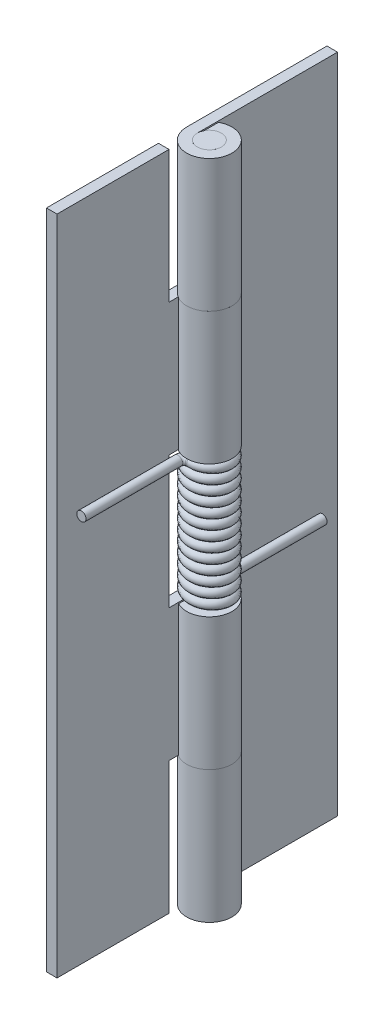
SolidWorks part; units mm, degrees
note: The reader was unsure of these and kept them because the rebuilt part matched: shared geometry of "Sketch12<2>", "Sketch13<2>".
ref_plane "Front Plane" through (0, 0, 0) normal (0, 0, 1) x (1, 0, 0)
ref_plane "Top Plane" through (0, 0, 0) normal (0, 1, 0) x (1, 0, 0)
ref_plane "Right Plane" through (0, 0, 0) normal (1, 0, 0) x (0, 0, -1)
sketch "Sketch1" plane through (0, 0, 0) normal (1, 0, 0) x (0, 0, -1)
  line L0 (0, 0) -> (0, 63.5) construction
  line L1 (0, 0) -> (13.462, 0) construction
  line L2 (3.556, 12.7) -> (7.5184, 12.7) construction
  point P3 (5.5372, 12.7)
  point P5 (5.5372, 50.8)
  point P6 (0, 12.7)
  point P9 (-101.6, 63.5)
  point P10 (5.5372, 12.7)
  point P11 (-25.4, 63.5)
  point P12 (-127, 63.5)
  dimension "D1" = 12.7
  dimension "Knuckle Length" = 12.7
  dimension "Length Corner" = 12.7
  dimension "Height Corner" = 7.9248
  dimension "Overall Width" = 26.924
  dimension "Leaf Height" = 63.5
  dimension "MTG Dia" = 3.9624
  dimension "Num Holes" = 101.6
  dimension "Spring Knuckles" = 25.4
  dimension "Num Knuckles" = 127
sketch "Sketch2" plane through (0, 0, 0) normal (0, 1, 0) x (1, 0, 0)
  line L0 (1.016, 0) -> (3.3274, 0) construction
  line L1 (0, 13.462) -> (1.016, 13.462) construction
  line L2 (1.016, 11.5697) -> (1.905, 11.5697) construction
  line L3 (2.1717, 1.1557) -> (2.1717, 2.1717) construction
  line L5 (2.1717, 2.1717) -> (2.1717, 11.5697) construction
  circle A0 centre (2.1717, 0) radius 1.1557 construction
  point P9 (2.1717, 1.2827)
  point P10 (1.143, 11.5697)
  dimension "Leaf Thickness" = 1.016
  dimension "Pin Dia" = 2.3114
  dimension "Wire Dia" = 0.889
  dimension "Spring Leg Length" = 9.398
  dimension "Bend Clearence" = 0.127
  dimension "D1" = 0.889
  dimension "Open Close Offset" = 0.127
sketch "Sketch3" plane through (0, 0, 0) normal (0, 1, 0) x (1, 0, 0)
  line L0 (1.016, 13.462) -> (0, 13.462)
  line L1 (0, 13.462) -> (0, 0)
  line L2 (0, 0) -> (0, 13.462) construction
  line L3 (1.016, 13.462) -> (1.016, 0)
  line L4 (1.143, 1.9126) -> (1.143, 0.5267)
  arc A0 (0, 0) -> (1.143, 1.9126) centre (2.1717, 0) ccw
  arc A1 (1.016, 0) -> (1.143, 0.5267) centre (2.1717, 0) ccw
extrude "Boss-Extrude1" add sketch "Sketch3" along normal up to vertex (63.5 mm away) up to point (0, 63.5, 0)
sketch "Sketch4" plane through (0, 0, 0) normal (0, 1, 0) x (1, 0, 0)
  line L0 (0, 0) -> (0, -13.462)
  line L1 (0, -13.462) -> (1.016, -13.462)
  line L2 (1.016, -13.462) -> (1.016, 0)
  line L3 (1.143, -0.5267) -> (1.143, -1.9126)
  line L4 (1.016, 0) -> (3.3274, 0) construction
  line L5 (0, 0) -> (0, 13.462) construction
  arc A0 (1.143, -1.9126) -> (0, 0) centre (2.1717, 0) ccw
  arc A1 (1.143, -0.5267) -> (1.016, 0) centre (2.1717, 0) ccw
extrude "Boss-Extrude2" add sketch "Sketch4" along normal up to vertex (63.5 mm away) separate body up to point (0, 63.5, 0)
sketch "Sketch7" plane through (0, 0, 0) normal (1, 0, 0) x (0, 0, -1)
  line L0 (-2.7102, 76.2) -> (2.7102, 76.2)
  line L1 (-2.7102, 25.4) -> (2.7102, 25.4)
  line L2 (-2.7102, 25.4) -> (-2.7102, 12.7)
  line L3 (-2.7102, 12.7) -> (2.7102, 12.7)
  line L4 (2.7102, 25.4) -> (2.7102, 12.7)
  line L5 (-2.7102, 50.8) -> (2.7102, 50.8)
  line L6 (-2.7102, 50.8) -> (-2.7102, 38.1)
  line L7 (2.7102, 50.8) -> (2.7102, 38.1)
  line L8 (-2.7102, 38.1) -> (2.7102, 38.1)
  line L9 (-2.7102, 25.4) -> (-2.7102, 50.8) construction
  line L10 (-2.7102, 76.2) -> (-2.7102, 63.5)
  line L11 (2.7102, 76.2) -> (2.7102, 63.5)
  line L12 (-2.7102, 63.5) -> (2.7102, 63.5)
  point P5 (0, 12.7)
  dimension "D1" = 12.7
  dimension "D2" = 5.4204
  dimension "D4" = 25.4
  dimension "D3" = 3
extrude "Cut-Extrude2" cut sketch "Sketch7" along normal through all
sketch "Sketch8" plane through (0, 0, 0) normal (1, 0, 0) x (0, 0, -1)
  line L0 (-2.7102, 12.7) -> (2.7102, 12.7) construction
  line L1 (-2.7102, 12.7) -> (2.7102, 12.7)
  line L2 (-2.7102, 12.7) -> (-2.7102, 0)
  line L3 (-2.7102, 0) -> (2.7102, 0)
  line L4 (2.7102, 12.7) -> (2.7102, 0)
  line L5 (-2.7102, 25.4) -> (-2.7102, 12.7) construction
  line L6 (-2.7102, 38.1) -> (2.7102, 38.1)
  line L7 (-2.7102, 38.1) -> (-2.7102, 25.4)
  line L8 (-2.7102, 25.4) -> (2.7102, 25.4)
  line L9 (2.7102, 38.1) -> (2.7102, 25.4)
  line L10 (-2.7102, 12.7) -> (-2.7102, 38.1) construction
  line L11 (-2.7102, 63.5) -> (2.7102, 63.5)
  line L12 (-2.7102, 63.5) -> (-2.7102, 50.8)
  line L13 (-2.7102, 50.8) -> (2.7102, 50.8)
  line L14 (2.7102, 63.5) -> (2.7102, 50.8)
  dimension "D2" = 25.4
extrude "Cut-Extrude3" cut sketch "Sketch8" along normal through all
sketch "Sketch10" plane through (0, 0, 0) normal (1, 0, 0) x (0, 0, -1)
  line L1 (2.7102, 38.1) -> (-2.7102, 38.1)
  line L2 (2.7102, 38.1) -> (2.7102, 25.4)
  line L3 (2.7102, 25.4) -> (-2.7102, 25.4)
  line L4 (-2.7102, 38.1) -> (-2.7102, 25.4)
  line L5 (-2.7102, 12.7) -> (2.7102, 12.7) construction
  line L7 (0, 0) -> (0, 63.5) construction
  point P4 (0, 25.4)
  dimension "D1" = 12.7
  dimension "D2" = 25.4
extrude "Cut-Extrude4" cut sketch "Sketch10" along normal through all
sketch "Sketch9" plane through (0, 0, 0) normal (0, 1, 0) x (1, 0, 0)
  line L0 (1.016, 0) -> (3.3274, 0) construction
  circle A0 centre (2.1717, 0) radius 1.1557
extrude "Boss-Extrude3" add sketch "Sketch9" along normal up to vertex (63.5 mm away) separate body up to point (0, 63.5, 0)
ref_plane "Plane1" through (0, 25.8445, 0) normal (0, 1, 0) x (1, 0, 0)
sketch "Sketch11" plane through (0, 25.8445, 0) normal (0, 1, 0) x (1, 0, 0)
  circle A0 centre (2.1717, 0) radius 2.1717
curve "Helix/Spiral1" pitch 0.9449 height 11.811 turns 12.5
ref_plane "Plane2" through (0, 37.6555, 0) normal (0, 1, 0) x (1, 0, 0)
sketch "Sketch12" plane through (0, 25.8445, 0) normal (0, 1, 0) x (1, 0, 0)
  line L0 (1.905, 11.5697) -> (1.905, 2.3051)
  line L1 (2.1717, 2.1717) -> (2.0383, 2.1717)
  line L2 (1.016, 11.5697) -> (1.905, 11.5697) construction
  line L3 (2.0383, 2.3051) -> (2.0383, 2.1717) construction
  arc A0 (2.0383, 2.1717) -> (1.905, 2.3051) centre (2.0383, 2.3051) cw
sketch "Sketch13" plane through (0, 37.6555, 0) normal (0, 1, 0) x (1, 0, 0)
  line L0 (1.905, -2.305) -> (1.905, -11.5697)
  line L1 (1.905, 11.5697) -> (1.905, 2.3051) construction
  line L2 (2.0383, -2.1717) -> (2.1717, -2.1717)
  line L3 (2.1717, 2.1717) -> (2.0383, 2.1717) construction
  arc A0 (1.905, -2.305) -> (2.0383, -2.1717) centre (2.0383, -2.305) cw
  circle A2 centre (2.1717, 0) radius 2.1717 construction
curve "CompCurve1"
ref_plane "Plane3" through (0, 0, -11.5697) normal (0, 0, 1) x (1, 0, 0)
sketch "Sketch14" plane through (0, 0, -11.5697) normal (0, 0, 1) x (1, 0, 0)
  line L0 (1.4605, 0) -> (1.4605, 25.8445) construction
  line L1 (1.016, 0) -> (1.905, 0) construction
  line L3 (4.3434, 25.8445) -> (0, 25.8445) construction
  circle A0 centre (1.4605, 25.8445) radius 0.4445
  dimension "D1" = 0.889
sweep "Sweep1" add profiles "Sketch14" path "Sketch12<2>"
sketch "Sketch12<2>" plane through (0, 25.8445, 0) normal (0, 1, 0) x (1, 0, 0) same geometry as "Sketch12"
sketch "Sketch15" plane through (2.1717, 0, 0) normal (1, 0, 0) x (0, 0, -1)
  circle A0 centre (1.7272, 25.8445) radius 0.4445 construction
  circle A1 centre (1.7272, 25.8445) radius 0.4445
sweep "Sweep2" add profiles "Sketch15" path "Helix/Spiral1"
sketch "Sketch16" plane through (2.1717, 0, 0) normal (-1, 0, 0) x (0, 0, 1)
  circle A0 centre (1.7272, 37.6555) radius 0.4445 construction
  circle A1 centre (1.7272, 37.6555) radius 0.4445
sweep "Sweep3" add profiles "Sketch16" path "Sketch13<2>"
sketch "Sketch13<2>" plane through (0, 37.6555, 0) normal (0, 1, 0) x (1, 0, 0) same geometry as "Sketch13"
equation "\"Num Knuckles\"=5"
equation "\"D1@Sketch7\"=\"Knuckle Length@Sketch1\""
equation "\"D2@Sketch7\" = ( 2 * \"Leaf Thickness@Sketch2\" ) + \"Pin Dia@Sketch2\" + ( .04 * \"Overall Width@Sketch1\" )"
equation "\"D4@Sketch7\"=\"Knuckle Length@Sketch1\"*2"
equation "\"D3@Sketch7\" = int ( \"Num Knuckles@Sketch1\" / 2 )  + 1"
equation "\"D2@Sketch8\"=\"D4@Sketch7\""
equation "\"D1@Sketch8\"=\"D3@Sketch7\""
equation "\"Spring Knuckles\"= 1"
equation "\"D1@Sketch10\"= \"Knuckle Length@Sketch1\" * \"Spring Knuckles@Sketch1\""
equation "\"D2@Sketch10\"=\"Knuckle Length@Sketch1\"*(\"Num Knuckles@Sketch1\"-\"Spring Knuckles@Sketch1\")/2"
equation "\"D1@Plane1\"=\"D2@Sketch10\"+(\"Wire Dia@Sketch2\"/2)"
equation "\"D3@Helix/Spiral1\"=(\"Spring Knuckles@Sketch1\"*\"Knuckle Length@Sketch1\")-\"Wire Dia@Sketch2\""
equation "\"D1@Plane2\"=\"D3@Helix/Spiral1\""
equation "\"D1@Sketch14\"=\"Wire Dia@Sketch2\""
equation "\"Num Holes\"=4"
equation "\"D1@Sketch1\"=\"Length Corner@Sketch1\""
equation "\"D1@Sketch2\"= \"Wire Dia@Sketch2\""
equation "\"Knuckle Length@Sketch1\"=\"Leaf Height@Sketch1\"/\"Num Knuckles@Sketch1\""
